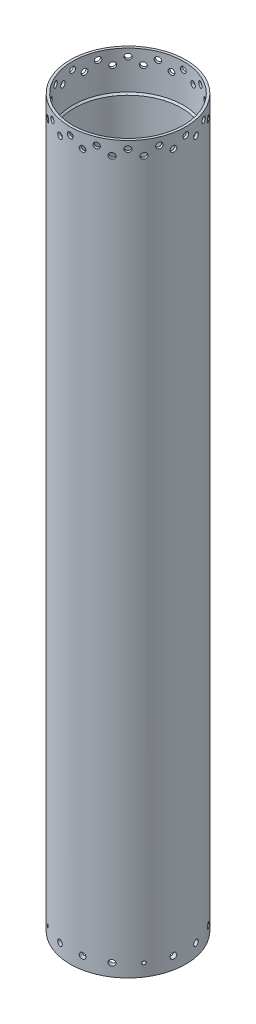
SolidWorks part; units mm, degrees
material "Stop 6061"
ref_plane "Płaszczyzna przednia" through (0, 0, 0) normal (0, 0, 1) x (1, 0, 0)
ref_plane "Płaszczyzna górna" through (0, 0, 0) normal (0, 1, 0) x (1, 0, 0)
ref_plane "Płaszczyzna prawa" through (0, 0, 0) normal (1, 0, 0) x (0, 0, -1)
sketch "Szkic1" plane through (0, 0, 0) normal (0, 0, 1) x (1, 0, 0)
  line L0 (0, 552.4394) -> (0, -579.7933) construction
  line L1 (70, -438.5) -> (70, 438.5)
  line L2 (70, 438.5) -> (67, 438.5)
  line L3 (67, 438.5) -> (67, 390.5)
  line L4 (67, 390.5) -> (65, 390.5)
  line L5 (65, 390.5) -> (65, -438.5)
  line L6 (65, -438.5) -> (70, -438.5)
  point P10 (70, 0)
  dimension "D1" = 877
  dimension "D2" = 5
  dimension "D3" = 48
  dimension "D4" = 3
  dimension "D5" = 65
revolve "Obrót1" add sketch "Szkic1" angle 360 about L0
chamfer "Sfazowanie1" distance 2 angle 45 1 edges at (0, 390.5, 67)
ref_plane "Płaszczyzna1" through (0, 0, 70) normal (0, 0, 1) x (1, 0, 0)
sketch "Szkic4" plane through (0, 0, 70) normal (0, 0, 1) x (1, 0, 0)
  line L0 (0, 438.5) -> (0, -438.5) construction
  line L1 (70, 438.5) -> (-70, 438.5) construction
  line L2 (-70, -438.5) -> (70, -438.5) construction
  circle A0 centre (0, 429.5) radius 3.5
  dimension "9" = 9
ref_plane "Płaszczyzna2" through (-13.6563, 0, 68.655) normal (-0.1951, 0, 0.9808) x (0, 1, 0)
sketch "Szkic6" plane through (-13.6563, 0, 68.655) normal (-0.1951, 0, 0.9808) x (0, 1, 0)
  line L0 (438.5, 0) -> (-438.5, 0) construction
  line L1 (438.5, -70) -> (438.5, 70) construction
  line L2 (-438.5, 70) -> (-438.5, -70) construction
  circle A0 centre (421.5, 0) radius 3.5
  dimension "D1" = 17
extrude "Wytnij-wyciągnięcie2" cut sketch "Szkic6" against normal blind 10
pattern_circular "Szyk kołowy2" count 16 over 360 about axis through (0, 552.4394, 0) along (0, 1, 0) of "Wytnij-wyciągnięcie2" reverse direction yes
extrude "Wytnij-wyciągnięcie4" cut sketch "Szkic4" against normal blind 10
pattern_circular "Szyk kołowy3" count 16 over 360 about axis through (0, 552.4394, 0) along (0, 1, 0) of "Wytnij-wyciągnięcie4" reverse direction yes
sketch "Szkic7" plane through (-13.6563, 0, 68.655) normal (-0.1951, 0, 0.9808) x (0, 1, 0)
  line L0 (438.5, 0) -> (-438.5, 0) construction
  line L1 (-438.5, 70) -> (-438.5, -70) construction
  line L2 (438.5, -70) -> (438.5, 70) construction
  circle A0 centre (-423.5, 0) radius 3.5
  dimension "D1" = 15
extrude "Wytnij-wyciągnięcie5" cut sketch "Szkic7" against normal blind 10
pattern_circular "Szyk kołowy4" count 3 over 45 about axis through (0, 552.4394, 0) along (0, 1, 0) of "Wytnij-wyciągnięcie5"
pattern_circular "Szyk kołowy5" count 4 over 360 about axis through (0, 552.4394, 0) along (0, 1, 0) of "Szyk kołowy4"
ref_plane "Płaszczyzna3" through (-58.2029, 0, -38.8899) normal (-0.8315, 0, -0.5556) x (0, 1, 0)
sketch "Szkic11" plane through (-58.2029, 0, -38.8899) normal (-0.8315, 0, -0.5556) x (0, 1, 0)
  line L0 (438.5, 0) -> (-438.5, 0) construction
  line L1 (-438.5, 70) -> (-438.5, -70) construction
  line L2 (438.5, -70) -> (438.5, 70) construction
  circle A0 centre (-423.5, 0) radius 2.05
  dimension "D1" = 15
  dimension "D2" = 4.1
extrude "Wytnij-wyciągnięcie6" cut sketch "Szkic11" against normal blind 10
pattern_circular "Szyk kołowy6" count 4 over 360 about axis through (0, 552.4394, 0) along (0, 1, 0) of "Wytnij-wyciągnięcie6"
